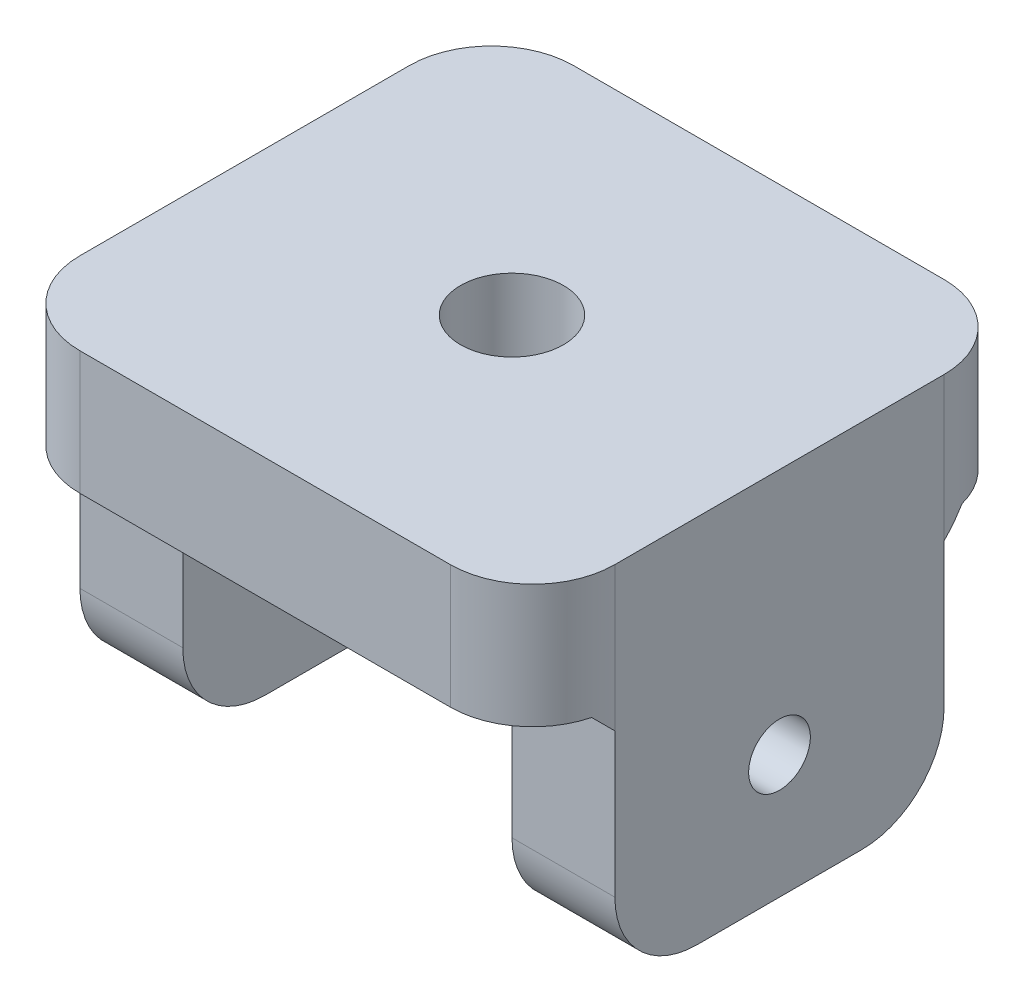
SolidWorks part; units mm, degrees
ref_plane "前视基准面" through (0, 0, 0) normal (0, 0, 1) x (1, 0, 0)
ref_plane "上视基准面" through (0, 0, 0) normal (0, 1, 0) x (1, 0, 0)
ref_plane "右视基准面" through (0, 0, 0) normal (1, 0, 0) x (0, 0, -1)
other "Configuration Table"
sketch "草图1" plane through (0, 0, 0) normal (0, 1, 0) x (1, 0, 0)
  line L1 (0, 0) -> (-26, 0)
  line L2 (0, 0) -> (0, 24)
  line L3 (0, 24) -> (-26, 24)
  line L4 (-26, 0) -> (-26, 24)
  dimension "D1" = 26
  dimension "D2" = 24
extrude "凸台-拉伸1" add sketch "草图1" along normal blind 6
sketch "草图2" plane through (0, 0, 0) normal (0, -1, 0) x (1, 0, 0)
  line L0 (-26, -24) -> (-26, 0) construction
  line L1 (-26, -4) -> (-21, -4)
  line L2 (-26, -4) -> (-26, -20)
  line L3 (-26, -20) -> (-21, -20)
  line L4 (-21, -4) -> (-21, -20)
  line L5 (0, 0) -> (0, -24) construction
  line L6 (0, -4) -> (-5, -4)
  line L7 (0, -4) -> (0, -20)
  line L8 (0, -20) -> (-5, -20)
  line L9 (-5, -4) -> (-5, -20)
  line L10 (-26, 0) -> (0, 0) construction
  dimension "D1" = 16
  dimension "D2" = 4
  dimension "D3" = 4
  dimension "D4" = 16
  dimension "D5" = 5
  dimension "D6" = 5
extrude "凸台-拉伸2" add sketch "草图2" along normal blind 12
sketch "草图3" plane through (-26, 0, 0) normal (-1, 0, 0) x (0, 0, 1)
  line L0 (-12, -12) -> (-12, -6) construction
  line L1 (-4, -12) -> (-20, -12) construction
  circle A0 centre (-12, -6) radius 1.5
  dimension "D2" = 3
  dimension "D1" = 6
extrude "切除-拉伸1" cut sketch "草图3" against normal blind 80
sketch "草图4" plane through (0, 6, 0) normal (0, 1, 0) x (1, 0, 0)
  line L0 (-26, 24) -> (0, 0) construction
  circle A0 centre (-13, 12) radius 2.5
  dimension "D1" = 5
extrude "切除-拉伸2" cut sketch "草图4" against normal blind 3.75
fillet "圆角1" radius 4 4 edges at (-26, 3, -24) (0, 3, -24) (0, 3, 0) (-26, 3, 0)
fillet "圆角2" radius 4 4 edges at (-2.5, -12, -4) (-2.5, -12, -20) (-23.5, -12, -20) (-23.5, -12, -4)
chamfer "倒角1" distance 1 angle 45 4 edges at (-2.5, 0, -20) (-23.5, 0, -20) (-2.5, 0, -4) (-23.5, 0, -4)
